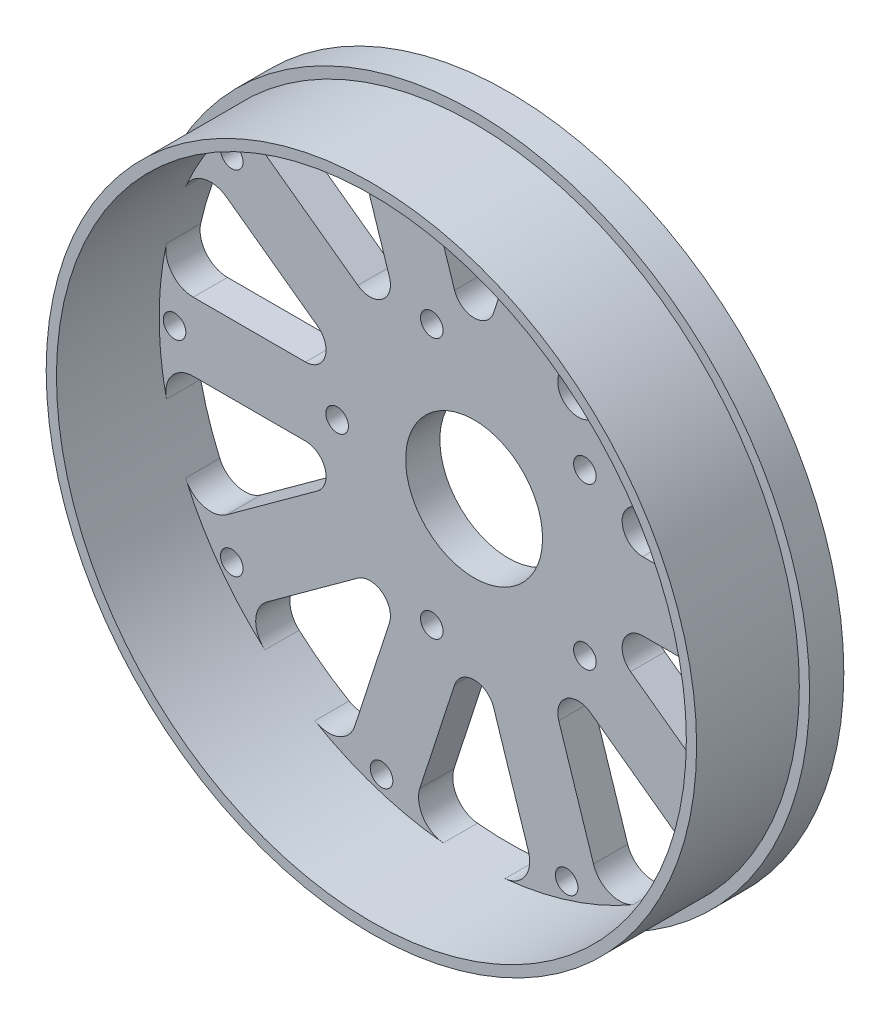
SolidWorks part; units mm, degrees
ref_plane "Front Plane" through (0, 0, 0) normal (0, 0, 1) x (1, 0, 0)
ref_plane "Top Plane" through (0, 0, 0) normal (0, 1, 0) x (1, 0, 0)
ref_plane "Right Plane" through (0, 0, 0) normal (1, 0, 0) x (0, 0, -1)
sketch "Sketch1" plane through (0, 0, 0) normal (0, 0, 1) x (1, 0, 0)
  line L0 (0, -1000) -> (0, 10) construction
  line L1 (-1000, 0) -> (49000, 0) construction
  line L2 (15.3884, 5) -> (48.7442, 5)
  line L3 (15.3884, -5) -> (48.7442, -5)
  line L4 (15.3884, -5) -> (42.3738, -24.6061)
  line L5 (9.5106, -13.0902) -> (36.496, -32.6962)
  line L6 (9.5106, -13.0902) -> (19.8181, -44.8134)
  line L7 (0, -16.1803) -> (10.3075, -47.9036)
  line L8 (0, -16.1803) -> (-10.3075, -47.9036)
  line L9 (-9.5106, -13.0902) -> (-19.8181, -44.8134)
  line L10 (-9.5106, -13.0902) -> (-36.496, -32.6962)
  line L11 (-15.3884, -5) -> (-42.3738, -24.6061)
  line L12 (-15.3884, -5) -> (-48.7442, -5)
  line L13 (-15.3884, 5) -> (-48.7442, 5)
  line L14 (-15.3884, 5) -> (-42.3738, 24.6061)
  line L15 (-9.5106, 13.0902) -> (-36.496, 32.6962)
  line L16 (-9.5106, 13.0902) -> (-19.8181, 44.8134)
  line L17 (0, 16.1803) -> (-10.3075, 47.9036)
  line L18 (0, 16.1803) -> (10.3075, 47.9036)
  line L19 (9.5106, 13.0902) -> (19.8181, 44.8134)
  line L20 (9.5106, 13.0902) -> (36.496, 32.6962)
  line L21 (15.3884, 5) -> (42.3738, 24.6061)
  line L22 (0, 16.1803) -> (0, 49000) construction
  circle A0 centre (0, 0) radius 47.5
  circle A1 centre (0, 0) radius 46
  circle A2 centre (0, 0) radius 49
  circle A3 centre (0, 0) radius 10
  point P52 (0, 0)
  dimension "D1" = 92
  dimension "D2" = 95
  dimension "D3" = 98
  dimension "D4" = 20
  dimension "D5" = 5
  dimension "D6" = 10
extrude "Boss-Extrude3" add sketch "Sketch1" along normal blind 15 contours A1 L14 A0 L13 | A1 L15 A0 L14 | A1 L16 A0 L15 | A1 L13 A0 L12 | A1 L12 A0 L11 | A1 L11 A0 L10 | A1 L17 A0 L16 | A1 L18 A0 L17 | A1 L19 A0 L18 | A1 L20 A0 L19 | A1 L21 A0 L20 | A1 L2 A0 L21 | A1 L3 A0 L2 | A1 L4 A0 L3 | A1 L5 A0 L4 | A1 L6 A0 L5 | A1 L7 A0 L6 | A1 L8 A0 L7 | A1 L9 A0 L8 | A1 L10 A0 L9 region at (44.1507, 14.3454, 0) region at (46.6606, 0, 0) region at (37.7492, 27.4264, 0) region at (27.2867, 37.5569, 0) region at (44.1507, -14.3454, 0) region at (14.4189, 44.3768, 0) region at (37.7492, -27.4264, 0) region at (0, 46.4228, 0) region at (27.2867, -37.5569, 0) region at (-14.4189, 44.3768, 0) region at (14.4189, -44.3768, 0) region at (-27.2867, 37.5569, 0) region at (0, -46.4228, 0) region at (-37.7492, 27.4264, 0) region at (-14.4189, -44.3768, 0) region at (-44.1507, 14.3454, 0) region at (-27.2867, -37.5569, 0) region at (-46.6606, 0, 0) region at (-37.7492, -27.4264, 0) region at (-44.1507, -14.3454, 0)
extrude "Boss-Extrude4" add sketch "Sketch1<6>" against normal blind 5 contours L17 A2 L16 A0 | L18 A2 L17 A0 | L19 A2 L18 A0 | L20 A2 L19 A0 | L21 A2 L20 A0 | L2 A2 L21 A0 | L3 A2 L2 A0 | L4 A2 L3 A0 | L5 A2 L4 A0 | L6 A2 L5 A0 | L7 A2 L6 A0 | L8 A2 L7 A0 | L9 A2 L8 A0 | L10 A2 L9 A0 | L11 A2 L10 A0 | L12 A2 L11 A0 | L13 A2 L12 A0 | L14 A2 L13 A0 | L15 A2 L14 A0 | L16 A2 L15 A0 | A1 L19 A0 L18 | A1 L20 A0 L19 | A1 L21 A0 L20 | A1 L2 A0 L21 | A1 L3 A0 L2 | A1 L4 A0 L3 | A1 L5 A0 L4 | A1 L6 A0 L5 | A1 L7 A0 L6 | A1 L8 A0 L7 | A1 L9 A0 L8 | A1 L10 A0 L9 | A1 L11 A0 L10 | A1 L12 A0 L11 | A1 L13 A0 L12 | A1 L14 A0 L13 | A1 L15 A0 L14 | A1 L16 A0 L15 | A1 L17 A0 L16 | A1 L18 A0 L17 | L21 A1 L20 L19 L18 L17 L16 L15 L14 L13 L12 L11 L10 L9 L8 L7 L6 L5 L4 L3 L2 A3 region at (30.5579, 3.7125, 0) region at (44.1507, 14.3454, 0) region at (46.6606, 0, 0) region at (37.7492, 27.4264, 0) region at (45.5563, 14.8021, 0) region at (48.1634, 0, 0) region at (38.965, 28.3097, 0) region at (27.2867, 37.5569, 0) region at (44.1507, -14.3454, 0) region at (28.1553, 38.7525, 0) region at (14.4189, 44.3768, 0) region at (45.5563, -14.8021, 0) region at (37.7492, -27.4264, 0) region at (14.8833, 45.8061, 0) region at (0, 46.4228, 0) region at (38.965, -28.3097, 0) region at (27.2867, -37.5569, 0) region at (0, 47.9007, 0) region at (-14.4189, 44.3768, 0) region at (28.1553, -38.7525, 0) region at (14.4189, -44.3768, 0) region at (-14.8833, 45.8061, 0) region at (-27.2867, 37.5569, 0) region at (14.8833, -45.8061, 0) region at (0, -46.4228, 0) region at (-28.1553, 38.7525, 0) region at (-37.7492, 27.4264, 0) region at (0, -47.9007, 0) region at (-14.4189, -44.3768, 0) region at (-38.965, 28.3097, 0) region at (-44.1507, 14.3454, 0) region at (-14.8833, -45.8061, 0) region at (-27.2867, -37.5569, 0) region at (-45.5563, 14.8021, 0) region at (-46.6606, 0, 0) region at (-28.1553, -38.7525, 0) region at (-37.7492, -27.4264, 0) region at (-48.1634, 0, 0) region at (-44.1507, -14.3454, 0) region at (-38.965, -28.3097, 0) region at (-45.5563, -14.8021, 0)
sketch "Sketch1<6>" plane through (0, 0, 0) normal (0, 0, 1) x (1, 0, 0) same geometry as "Sketch1"
fillet "Fillet1" radius 4 20 edges at (45.7275, 5, -2.5) (39.9332, 22.8328, -2.5) (18.8858, 41.9443, -2.5) (34.0554, 30.923, -2.5) (9.3753, 45.0345, -2.5) (-9.3753, 45.0345, -2.5) (-18.8858, 41.9443, -2.5) (-34.0554, 30.923, -2.5) (-45.7275, 5, -2.5) (-39.9332, 22.8328, -2.5) (-45.7275, -5, -2.5) (-39.9332, -22.8328, -2.5) (-34.0554, -30.923, -2.5) (-18.8858, -41.9443, -2.5) (9.3753, -45.0345, -2.5) (-9.3753, -45.0345, -2.5) (18.8858, -41.9443, -2.5) (34.0554, -30.923, -2.5) (45.7275, -5, -2.5) (39.9332, -22.8328, -2.5)
fillet "Fillet2" radius 3 10 edges at (0, 16.1803, -2.5) (-9.5106, 13.0902, -2.5) (-15.3884, 5, -2.5) (-15.3884, -5, -2.5) (-9.5106, -13.0902, -2.5) (0, -16.1803, -2.5) (9.5106, -13.0902, -2.5) (15.3884, -5, -2.5) (15.3884, 5, -2.5) (9.5106, 13.0902, -2.5)
sketch "Sketch2" plane through (0, 0, -5) normal (0, 0, -1) x (-1, 0, 0)
  line L0 (0, 0) -> (20, 0) construction
  line L1 (20, 0) -> (43.75, 0) construction
  circle A0 centre (0, 0) radius 20 construction
  circle A1 centre (0, 0) radius 43.75 construction
  dimension "D1" = 40
  dimension "D2" = 87.5
hole_wizard "M4x0.7 Tapped Hole1" positions "Sketch5" profile "Sketch4" tap size "M4x0.7" standard "ANSI Metric" end condition through all
sketch "Sketch5" plane through (0, 0, -5) normal (0, 0, -1) x (-1, 0, 0)
  point P0 (20, 0)
sketch "Sketch4" plane through (-20, 0, -5) normal (1, 0, 0) x (0, 1, 0)
  line L0 (0, 0) -> (0, 20)
  line L1 (0, 20) -> (1.65, 20)
  line L2 (1.65, 20) -> (1.65, 0)
  line L5 (1.65, 0) -> (0, 0)
  line L11 (0, -6.35) -> (0, 107.95) construction
  dimension "Thru Tap Drill Dia." = 3.3
  dimension "Thru Tap Drill Depth" = 20
cosmetic thread "Hole Thread1" parameters "D2"=4
sketch "Sketch6" plane through (0, 0, 0) normal (1, 0, 0) x (0, 0, -1)
  line L0 (-1000, 0) -> (49000, 0) construction
pattern_circular "CirPattern1" count 5 over 360 about axis through (0, 0, 1000) along (0, 0, -1) of "M4x0.7 Tapped Hole1"
cosmetic thread "Hole Thread2" parameters "D2"=4
cosmetic thread "Hole Thread3" parameters "D2"=4
cosmetic thread "Hole Thread4" parameters "D2"=4
cosmetic thread "Hole Thread5" parameters "D2"=4
cosmetic thread "Hole Thread6" parameters "D2"=4
cosmetic thread "Hole Thread7" parameters "D2"=4
cosmetic thread "Hole Thread8" parameters "D2"=4
cosmetic thread "Hole Thread9" parameters "D2"=4
cosmetic thread "Hole Thread10" parameters "D2"=4
hole_wizard "M4x0.7 Tapped Hole2" positions "Sketch7" profile "Sketch8" tap size "M4x0.7" standard "ANSI Metric" end condition through all
sketch "Sketch7" plane through (0, 0, -5) normal (0, 0, -1) x (-1, 0, 0)
  point P0 (43.75, 0)
sketch "Sketch8" plane through (-43.75, 0, -5) normal (1, 0, 0) x (0, 1, 0)
  line L0 (0, 0) -> (0, 20)
  line L1 (0, 20) -> (1.65, 20)
  line L2 (1.65, 20) -> (1.65, 0)
  line L5 (1.65, 0) -> (0, 0)
  line L11 (0, -6.35) -> (0, 107.95) construction
  dimension "Thru Tap Drill Dia." = 3.3
  dimension "Thru Tap Drill Depth" = 20
cosmetic thread "Hole Thread11" parameters "D2"=4
pattern_circular "CirPattern2" count 10 over 360 about axis through (0, 0, 1000) along (0, 0, -1) of "M4x0.7 Tapped Hole2"
cosmetic thread "Hole Thread12" parameters "D2"=4
cosmetic thread "Hole Thread13" parameters "D2"=4
cosmetic thread "Hole Thread14" parameters "D2"=4
cosmetic thread "Hole Thread15" parameters "D2"=4
cosmetic thread "Hole Thread16" parameters "D2"=4
cosmetic thread "Hole Thread17" parameters "D2"=4
cosmetic thread "Hole Thread18" parameters "D2"=4
cosmetic thread "Hole Thread19" parameters "D2"=4
cosmetic thread "Hole Thread20" parameters "D2"=4
